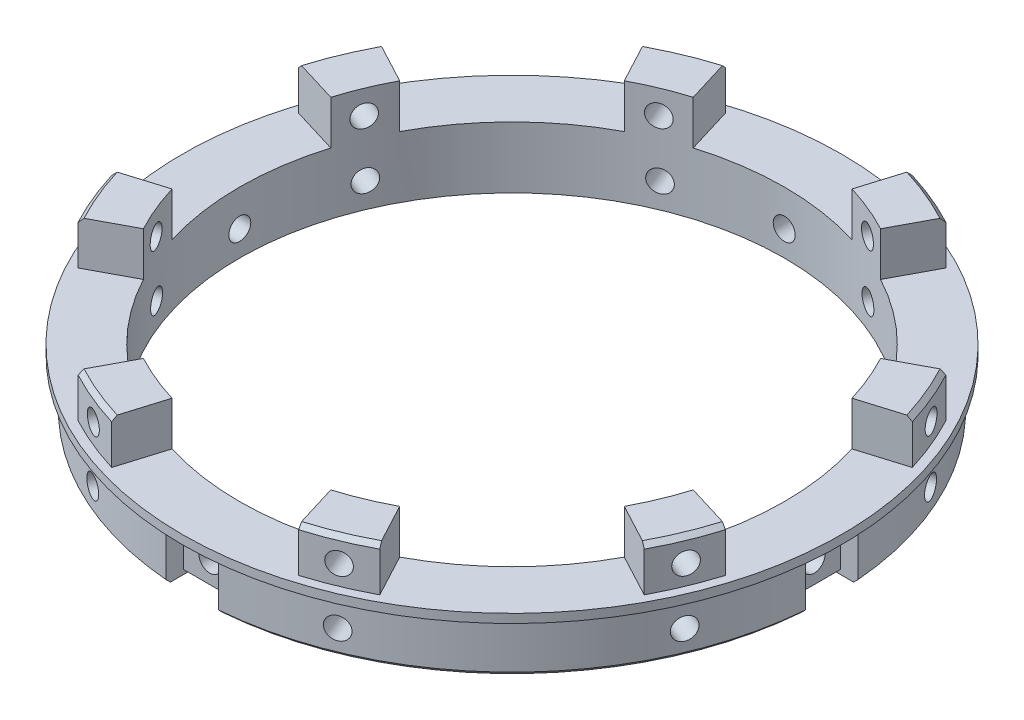
SolidWorks part; units mm, degrees
material "7075-T6, Piastra (SS)"
ref_plane "Piano frontale" through (0, 0, 0) normal (0, 0, 1) x (1, 0, 0)
ref_plane "Piano superiore" through (0, 0, 0) normal (0, 1, 0) x (1, 0, 0)
ref_plane "Piano destro" through (0, 0, 0) normal (1, 0, 0) x (0, 0, -1)
sketch "Schizzo1" plane through (0, 0, 0) normal (0, 0, 1) x (1, 0, 0)
  line L1 (-73, 24) -> (-62, 24)
  line L4 (0, 3) -> (0, 0)
  line L5 (0, 0) -> (-73, 0)
  line L7 (-73, 12) -> (-73, 0)
  line L10 (0, 0) -> (0, 105.2736) construction
  line L12 (-62, 3) -> (0, 3)
  line L13 (-73, 12) -> (-75, 12)
  line L14 (-75, 12) -> (-75, 14)
  line L15 (-75, 14) -> (-73, 14)
  line L16 (-73, 14) -> (-73, 24)
  line L19 (-62, 3) -> (-62, 0)
  line L20 (-62, 24) -> (-62, 3)
  dimension "D1" = 146
  dimension "D2" = 14
  dimension "D3" = 150
  dimension "D4" = 24
  dimension "D5" = 12
  dimension "D6" = 124
  dimension "D9" = 3
revolve "Rivoluzione1" add sketch "Schizzo1" angle 360 about L10 region at (-67.597, 12.0149, 0) region at (-31, 1.5, 0)
sketch "Schizzo2" plane through (0, 0, 0) normal (0, -1, 0) x (1, 0, 0)
  line L0 (0, 0) -> (-73, 0) construction
  line L1 (-72.753, 6) -> (-68.753, 6)
  line L2 (-68.753, 6) -> (-68.753, -6)
  line L3 (-68.753, -6) -> (-72.753, -6)
  circle A0 centre (0, 0) radius 73 construction
  arc A1 (-72.753, -6) -> (-72.753, 6) centre (0, 0) cw
  circle A2 centre (0, 0) radius 73 construction
  point P10 (-68.753, 0)
  dimension "D1" = 12
  dimension "D2" = 4
extrude "Taglio-Estrusione1" cut sketch "Schizzo2" against normal up to surface (12 mm away) up to face at (0, 12, -75)
sketch "Schizzo3" plane through (0, 24, 0) normal (0, 1, 0) x (1, 0, 0)
  line L0 (0, 0) -> (-73, 0) construction
  line L4 (0, 0) -> (-51.6188, 51.6188) construction
  line L7 (-43.8406, 43.8406) -> (-51.6188, 51.6188)
  line L8 (0, 0) -> (-67.4432, 27.9359) construction
  line L9 (0, 0) -> (-59.3078, 18.0717) construction
  line L10 (0, 0) -> (-54.7156, 29.1583) construction
  line L11 (-59.3078, 18.0717) -> (-69.8301, 21.278)
  line L12 (-54.7156, 29.1583) -> (-64.4232, 34.3315)
  line L13 (-59.3078, 18.0717) -> (-54.7156, 29.1583) construction
  line L14 (-62, 0) -> (-73, 0)
  circle A2 centre (0, 0) radius 62 construction
  arc A5 (-59.3078, 18.0717) -> (-43.8406, 43.8406) centre (0, 0) cw
  circle A6 centre (0, 0) radius 73 construction
  arc A7 (-69.8301, 21.278) -> (-51.6188, 51.6188) centre (0, 0) cw
  arc A8 (-69.8301, 21.278) -> (-64.4232, 34.3315) centre (0, 0) cw
  arc A9 (-62, 0) -> (-59.3078, 18.0717) centre (0, 0) cw
  arc A10 (-73, 0) -> (-69.8301, 21.278) centre (0, 0) cw
  point P19 (-57.0117, 23.615)
  circle M10 centre (0, 0) radius 62
  circle M11 centre (0, 0) radius 73
  dimension "D2" = 45
  dimension "D1" = 22.5
  dimension "D4" = 12
extrude "Taglio-Estrusione3" cut sketch "Schizzo3" against normal up to surface (10 mm away) contours L7 M10 M11 | L14 L11 M10 M11 region at (-54.1637, 24, -40.1181) region at (-66.6673, 24, -9.9317) up to face at (0, 14, -73)
hole_wizard "Foro Ø5.0 (5)-1" positions "Schizzo3D1" profile "Schizzo5" hole size "Ø5.0" standard "ISO"
sketch3d "Schizzo3D1"
  point P0 (-67.4812, 18.5213, -27.8441)
sketch "Schizzo5" plane through (-67.4812, 18.5213, -27.8441) normal (0, 1, 0) x (-0.3814, 0, 0.9244)
  line L0 (0, 0) -> (0, 19)
  line L1 (0, 19) -> (2.5, 17.4978)
  line L2 (2.5, 17.4978) -> (2.5, 0)
  line L5 (2.5, 0) -> (0, 0)
  line L10 (0, 19) -> (-2.5, 17.4978) construction
  line L11 (0, -6.35) -> (0, 107.95) construction
  dimension "Hole Dia." = 5
  dimension "Hole Depth" = 19
  dimension "Drill Angle" = 118
hole_wizard "Foro Ø5.0 (5)-2" positions "Schizzo6" profile "Schizzo7" hole size "Ø5.0" standard "ISO"
sketch "Schizzo6" plane through (-68.753, 0, 0) normal (-1, 0, 0) x (0, 0, 1)
  point P0 (0, 5.7708)
sketch "Schizzo7" plane through (-68.753, 5.7708, 0) normal (0, 1, 0) x (0, 0, 1)
  line L0 (0, 0) -> (0, 19)
  line L1 (0, 19) -> (2.5, 17.4978)
  line L2 (2.5, 17.4978) -> (2.5, 0)
  line L5 (2.5, 0) -> (0, 0)
  line L10 (0, 19) -> (-2.5, 17.4978) construction
  line L11 (0, -6.35) -> (0, 107.95) construction
  dimension "Hole Dia." = 5
  dimension "Hole Depth" = 19
  dimension "Drill Angle" = 118
chamfer "Smusso1" distance 1 angle 45 1 edges at (73, 0, 0)
chamfer "Smusso2" distance 1 angle 45 1 edges at (-68.753, 0, 0)
fillet "Raccordo1" radius 1 1 edges at (-68.753, 12, 0)
chamfer "Smusso3" distance 1 angle 45 1 edges at (-67.4432, 24, -27.9359)
pattern_circular "RipetizioneCircolare5" count 8 over 360 about axis through (0, 14, 0) along (0, -1, 0) of "Foro Ø5.0 (5)-1", "Smusso3", "Taglio-Estrusione3"
pattern_circular "RipetizioneCircolare6" count 4 over 360 about axis through (0, 12, 0) along (0, -1, 0) of "Taglio-Estrusione1", "Foro Ø5.0 (5)-2", "Raccordo1", "Smusso2"
hole_wizard "Foro Ø5.0 (5)-4" positions "Schizzo3D3" profile "Schizzo9" hole size "Ø5.0" standard "ISO"
sketch3d "Schizzo3D3"
  point P0 (-67.4973, 5.7088, 27.805)
  point P2 (-67.4973, 5.7088, 27.805)
sketch "Schizzo9" plane through (-67.4973, 5.7088, 27.805) normal (0, 1, 0) x (0.3809, 0, 0.9246)
  line L0 (0, 0) -> (0, 19)
  line L1 (0, 19) -> (2.5, 17.4978)
  line L2 (2.5, 17.4978) -> (2.5, 0)
  line L5 (2.5, 0) -> (0, 0)
  line L10 (0, 19) -> (-2.5, 17.4978) construction
  line L11 (0, -6.35) -> (0, 107.95) construction
  dimension "Hole Dia." = 5
  dimension "Hole Depth" = 19
  dimension "Drill Angle" = 118
pattern_circular "RipetizioneCircolare7" count 8 over 360 about axis through (0, 1, 0) along (0, 1, 0) of "Foro Ø5.0 (5)-4"
sketch "Schizzo10" plane through (0, 3, 0) normal (0, 1, 0) x (1, 0, 0)
  circle A0 centre (0, 0) radius 62
  arc A1 (-29.1583, 54.7156) -> (-54.7156, 29.1583) centre (0, 0) ccw construction
extrude "Taglio-Estrusione4" cut sketch "Schizzo10" against normal blind 10
